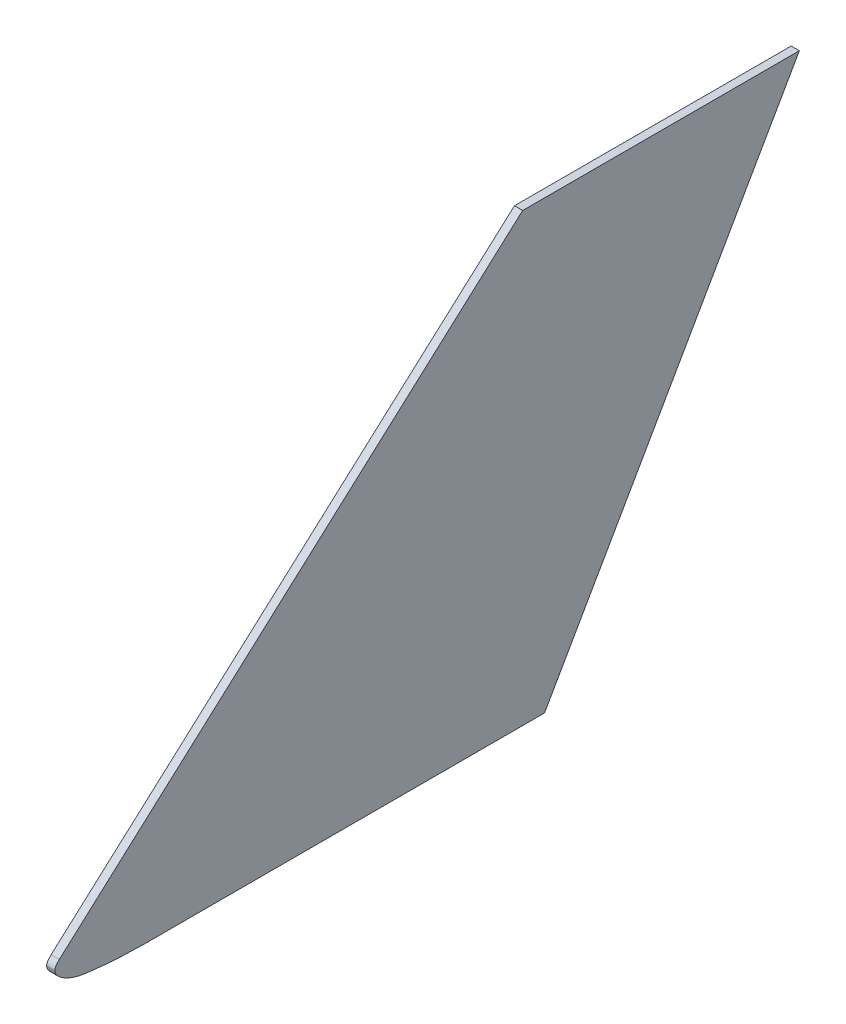
SolidWorks part; units mm, degrees
material "ABS Winglet Material"
ref_plane "Front Plane" through (0, 0, 0) normal (0, 0, 1) x (1, 0, 0)
ref_plane "Top Plane" through (0, 0, 0) normal (0, 1, 0) x (1, 0, 0)
ref_plane "Right Plane" through (0, 0, 0) normal (1, 0, 0) x (0, 0, -1)
sketch "Sketch1" plane through (0, 0, 0) normal (1, 0, 0) x (0, 0, -1)
  line L0 (0, 0) -> (168.275, 0)
  line L1 (168.275, 0) -> (251.079, 145)
  line L2 (251.079, 145) -> (161.163, 145)
  line L3 (161.163, 145) -> (0, 0)
  dimension "D1" = 168.275
  dimension "D2" = 145
  dimension "D3" = 82.804
  dimension "D4" = 89.916
extrude "Boss-Extrude1" add sketch "Sketch1" along normal blind 2.667
sketch "Sketch2" plane through (0, 0, 0) normal (-1, 0, 0) x (0, 0, 1)
  line L0 (-58.3067, 0.4912) -> (-40.9692, 0) construction
  line L1 (-131.2701, 15.9151) -> (-125.292, 4.987) construction
  line L2 (-125.292, 4.987) -> (-96.5991, 2.5788) construction
  line L3 (-96.5991, 2.5788) -> (-58.3067, 0.4912) construction
  line L4 (-58.3067, 0.4912) -> (-40.9692, 0) construction
  line L5 (-131.2701, 15.9151) -> (-125.292, 4.987) construction
  line L6 (-125.292, 4.987) -> (-96.5991, 2.5788) construction
  line L7 (-96.5991, 2.5788) -> (-58.3067, 0.4912) construction
  line L8 (-38.2685, 0) -> (1.6038, -0.1367)
  line L10 (-10.613, 9.4828) -> (-7.657, 9.4828)
  line L11 (-7.657, 9.4828) -> (1.6038, -0.1367)
  line L12 (1.6038, -0.1367) -> (1.6562, -0.0616)
  parabola Q0 (-38.2685, 0) -> (-20.4792, 1.1041) focus (-33.037, 71.6752) apex (-27.8636, 0.3753) construction
  parabola Q1 (-38.2685, 0) -> (-20.4792, 1.1041) focus (-33.037, 71.6752) apex (-27.8636, 0.3753)
  spline S0 degree 3 poles (2947.4765, -434.3435) (-73.4571, 47.0874) (5.3401, -77.8318) (37.3208, 136.5775) (-2863.4158, -910.5095) knots -0.404526 -0.404526 -0.404526 -0.404526 0.031804 0.647576 0.647576 0.647576 0.647576 only from (-20.4792, 1.1041) to (-9.0961, 6.9651) construction
  spline S2 degree 3 poles (-20.4792, 1.1041) (-19.7842, 1.1909) (-14.2944, 1.6921) (-9.1863, 4.9601) (-9.0961, 6.9651) knots 0 0 0 0 0.031804 0.095003 0.095003 0.095003 0.095003
  spline S3 degree 3 poles (-3007.8046, 48.534) (86.7182, -53.9587) (-0.8607, 12.5217) (-41.7081, 18.8012) (-289.6607, 26.8358) (-387.7551, -104.9376) (-2759.3658, -1429.6415) knots -0.467092 -0.467092 -0.467092 -0.467092 0.16879 0.324837 0.583849 5.286023 5.286023 5.286023 5.286023 only from (-9.0961, 6.9651) to (-131.2701, 15.9151) construction
  spline S4 degree 3 poles (-9.0961, 6.9651) (-9.0567, 7.842) (-9.65, 8.6866) (-10.613, 9.4828) knots 0.095003 0.095003 0.095003 0.095003 0.122644 0.122644 0.122644 0.122644
  line M4 (-168.275, 0) -> (0, 0)
extrude "Cut-Extrude1" cut sketch "Sketch2" against normal through all contours S2 Q1 M4 region at (0, 2.7245, -9.4152)
